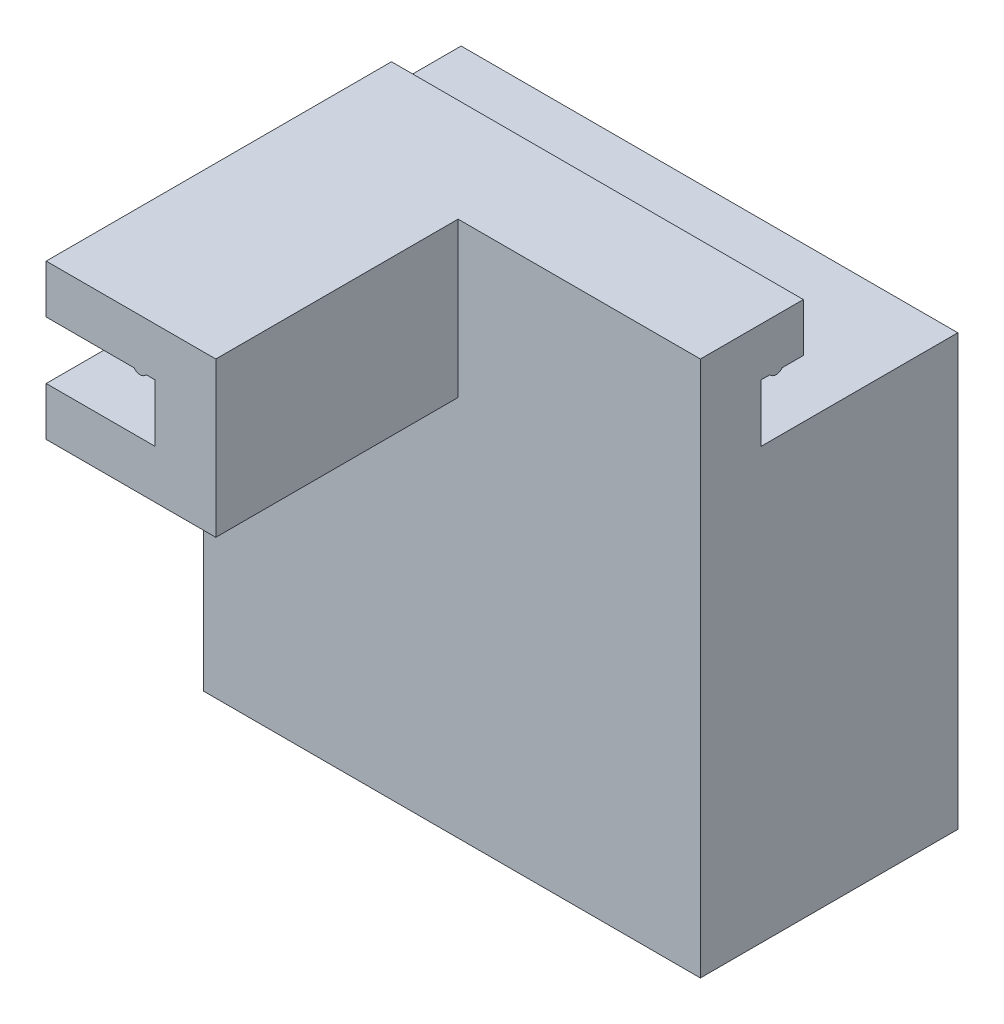
SolidWorks part; units mm, degrees
ref_plane "Front Plane" through (0, 0, 0) normal (0, 0, 1) x (1, 0, 0)
ref_plane "Top Plane" through (0, 0, 0) normal (0, 1, 0) x (1, 0, 0)
ref_plane "Right Plane" through (0, 0, 0) normal (1, 0, 0) x (0, 0, -1)
sketch "Sketch1" plane through (0, 0, 0) normal (0, 0, 1) x (1, 0, 0)
  line L0 (0, 0) -> (-18, 0)
  line L1 (-18, 0) -> (-18, -8)
  line L2 (-18, -8) -> (0, -8)
  line L3 (0, -8) -> (0, -17.5)
  line L4 (0, -17.5) -> (-18, -17.5)
  line L5 (-18, -17.5) -> (-18, -25.5)
  line L6 (-18, -25.5) -> (10, -25.5)
  line L7 (10, -25.5) -> (10, 0)
  line L8 (10, 0) -> (0, 0)
  arc A0 (-3.5, -8) -> (-1.5, -8) centre (-2.5, -7.25) ccw
  point P13 (-2.5, -8.5)
  dimension "D7" = 2.5
  dimension "D1" = 18
  dimension "D2" = 9.5
  dimension "D3" = 8
  dimension "D4" = 8
  dimension "D5" = 10
  dimension "D6" = 9
  dimension "D8" = 1
  dimension "D9" = 28
extrude "Boss-Extrude1" add sketch "Sketch1" along normal blind 50 contours L2 A0 | L7 L8 L0 L1 L2 L3 L4 L5 L6 region at (5, -0.3787, 0) region at (-2.5, -8.2039, 0)
sketch "Sketch2" plane through (0, 0, 0) normal (1, 0, 0) x (0, 0, -1)
  line L9 (0, 0) -> (0, -50) construction
  line L10 (7, -8) -> (0, -8)
  line L11 (0, -17.5) -> (7, -17.5)
  line L12 (0, -8) -> (0, -17.5)
  line L13 (7, -17.5) -> (7, -25.5)
  line L14 (7, -25.5) -> (-10, -25.5)
  line L15 (-10, -25.5) -> (-10, 0)
  line L16 (-10, 0) -> (0, 0)
  line L17 (0, 0) -> (7, 0)
  line L18 (7, 0) -> (7, -8)
  arc A1 (3.5, -8) -> (1.5, -8) centre (2.5, -7.25) cw
  point P0 (8, 0)
  point P1 (0, 0)
  point P13 (0, 0.2464)
  point P14 (-0.364, -46.736)
  point P16 (0, -49.2723)
  dimension "D13" = 1.25
  dimension "D2" = 17
  dimension "D4" = 25.5
  dimension "D5" = 1
  dimension "D6" = 9.5
  dimension "D7" = 8
  dimension "D8" = 8
  dimension "D9" = 10
  dimension "D10" = 10
  dimension "D11" = 50
  dimension "D12" = 7
  dimension "D14" = 2.5
  dimension "D15" = 1.5
  dimension "D16" = 0.75
extrude "Boss-Extrude2" add sketch "Sketch2" along normal blind 50 contours L17 L9 L10 L18 | L9 L16 L15 L14 L12 | L11 L9 L14 L13 | A1 L10 region at (0, -4, -3.5) region at (0, -12.75, 5) region at (0, -21.5, -3.5) region at (0, -8.2039, -2.5)
extrude "Boss-Extrude3" add sketch "Sketch2<3>" against normal up to surface (18 mm away) contours L17 L9 L10 L18 | L11 L9 L14 L13 region at (0, -4, -3.5) region at (0, -21.5, -3.5) up to face at (-18, -4, 25)
sketch "Sketch2<3>" plane through (0, 0, 0) normal (1, 0, 0) x (0, 0, -1) same geometry as "Sketch2"
sketch "Sketch3" plane through (50, 0, 0) normal (1, 0, 0) x (0, 0, -1)
  line L0 (0, -17.5) -> (32.5, -17.5)
  line L1 (0, -25.5) -> (0, -88.5)
  line L2 (7, -25.5) -> (-10, -25.5) construction
  line L3 (0, -17.5) -> (0, -25.5)
  line L4 (32.5, -17.5) -> (32.5, -88.5)
  line L5 (32.5, -88.5) -> (0, -88.5)
  line L6 (0, -17.5) -> (-10, -17.5)
  line L7 (-10, -25.5) -> (-10, 0) construction
  line L8 (-10, -17.5) -> (-10, -88.5)
  line L9 (-10, -88.5) -> (0, -88.5)
  line M3 (-10, 0) -> (-10, -25.5)
  line M4 (-10, -25.5) -> (7, -25.5)
  line M5 (7, -25.5) -> (7, -17.5)
  line M6 (7, -17.5) -> (0, -17.5)
  dimension "D1" = 32.5
  dimension "D2" = 63
ref_plane "Wall" through (-32, 0, 0) normal (-1, 0, 0) x (0, 0, 1)
extrude "Boss-Extrude4" add sketch "Sketch3" against normal up to surface (82 mm away) contours L5 L4 L0 L1 M5 M4 | L8 L9 L1 M4 | L3 M6 M4 M5 | L3 L6 M3 M4 region at (50, -21.5, -3.5) region at (50, -21.5, 5) region at (50, -53.7835, -16.5671) region at (50, -57, 5) up to plane "Wall"
